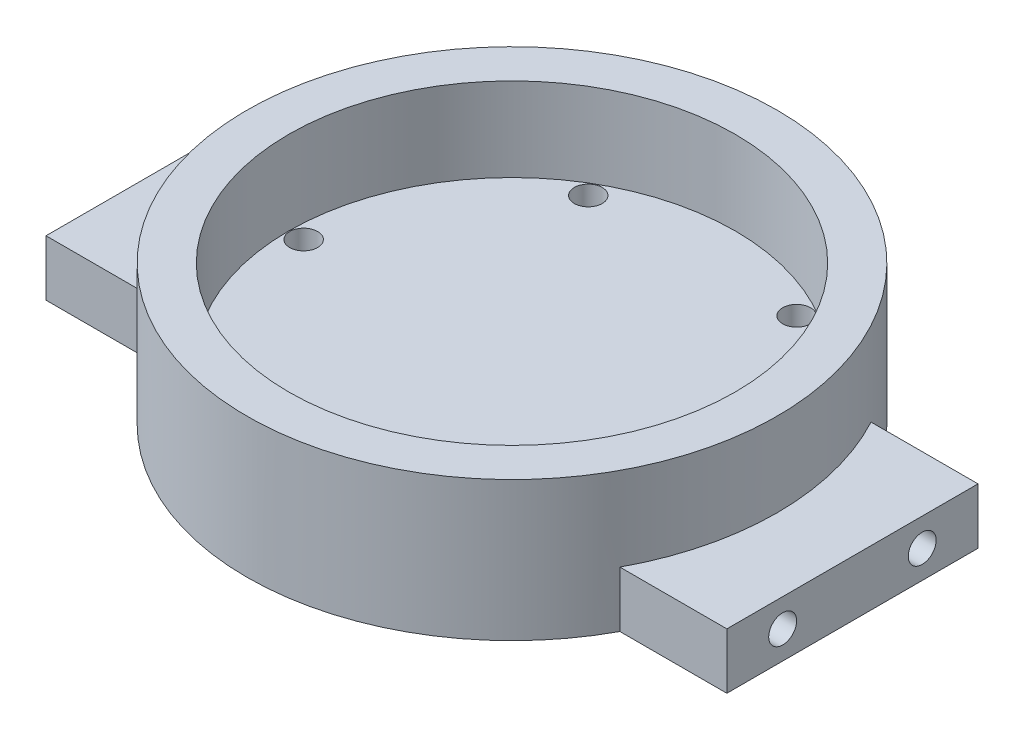
SolidWorks part; units mm, degrees
ref_plane "Front Plane" through (0, 0, 0) normal (0, 0, 1) x (1, 0, 0)
ref_plane "Top Plane" through (0, 0, 0) normal (0, 1, 0) x (1, 0, 0)
ref_plane "Right Plane" through (0, 0, 0) normal (1, 0, 0) x (0, 0, -1)
sketch "Sketch7" plane through (0, 0, 0) normal (0, 1, 0) x (1, 0, 0)
  line L1 (-61, 0) -> (61, 0)
  line L2 (-61, 0) -> (-61, 45)
  line L3 (-61, 45) -> (61, 45)
  line L4 (61, 0) -> (61, 45)
  dimension "D1" = 45
  dimension "D2" = 122
extrude "Boss-Extrude1" add sketch "Sketch7" along normal blind 10
sketch "Sketch8" plane through (61, 0, 0) normal (1, 0, 0) x (0, 0, -1)
  line L0 (10, 5) -> (35, 5) construction
  line L1 (0, 10) -> (0, 0) construction
  line L2 (0, 0) -> (45, 0) construction
  circle A0 centre (10, 5) radius 2.5
  circle A1 centre (35, 5) radius 2.5
  point P7 (0, 5)
  point P10 (22.5, 0)
  point P11 (22.5, 5)
  dimension "D1" = 5
  dimension "D2" = 25
extrude "Cut-Extrude3" cut sketch "Sketch8" against normal blind 25
mirror "Mirror1" about plane through (0, 0, 0) normal (1, 0, 0) of "Cut-Extrude3"
sketch "Sketch9" plane through (0, 10, 0) normal (0, 1, 0) x (1, 0, 0)
  line L0 (-61, 45) -> (-61, 0) construction
  circle A0 centre (0, 22.5) radius 37.333 construction
  circle A1 centre (0, 22.5) radius 42.333
  circle A2 centre (-37.333, 22.5) radius 2.5
  circle A3 centre (-18.6665, 54.8313) radius 2.5
  circle A4 centre (18.6665, 54.8313) radius 2.5
  circle A5 centre (37.333, 22.5) radius 2.5
  circle A6 centre (18.6665, -9.8313) radius 2.5
  circle A7 centre (-18.6665, -9.8313) radius 2.5
  point P6 (-61, 22.5)
  dimension "D1" = 74.666
  dimension "D2" = 5
  dimension "D3" = 5
  dimension "D4" = 6
extrude "Boss-Extrude2" add sketch "Sketch9" against normal up to surface (10 mm away) up to face at (0, 0, -22.5)
extrude "Cut-Extrude4" cut sketch "Sketch9<2>" against normal through all contours A2 | A5
sketch "Sketch9<2>" plane through (0, 10, 0) normal (0, 1, 0) x (1, 0, 0) same geometry as "Sketch9"
sketch "Sketch10" plane through (0, 0, 0) normal (0, -1, 0) x (1, 0, 0)
  circle A0 centre (0, -22.5) radius 40
  arc A1 (35.8585, 0) -> (-35.8585, 0) centre (0, -22.5) ccw construction
  circle A2 centre (0, -22.5) radius 47.5
  line M5 (-61, -45) -> (-35.8585, -45)
  arc M6 (-35.8585, -45) -> (35.8585, -45) centre (0, -22.5) ccw
  line M7 (35.8585, -45) -> (61, -45)
  line M9 (61, 0) -> (35.8585, 0)
  arc M10 (35.8585, 0) -> (-35.8585, 0) centre (0, -22.5) ccw
  line M11 (-35.8585, 0) -> (-61, 0)
  dimension "D1" = 80
  dimension "D2" = 7.5
extrude "Boss-Extrude3" add sketch "Sketch10" against normal blind 25 contours A2 M5 M7 M6 | A2 A0 M7 M9 M10 M11 M5 M6 | A2 M9 M11 M10 | A2 | A0 region at (44.8275, 0, -33.7905) region at (38.8458, 0, 0.8732) region at (0, 0, -69.1268)
